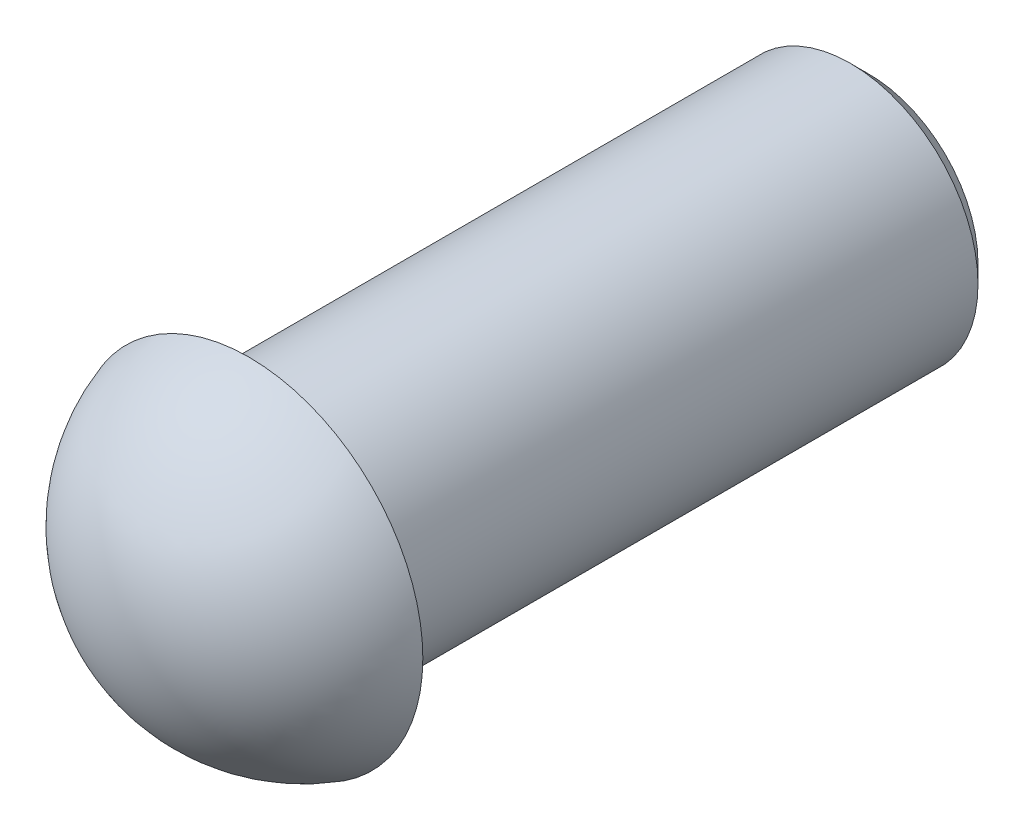
SolidWorks part; units mm, degrees
ref_plane "Plan d'appui" through (0, 0, 0) normal (0, 0, 1) x (1, 0, 0)
ref_plane "Dessus" through (0, 0, 0) normal (0, 1, 0) x (1, 0, 0)
ref_plane "Droite" through (0, 0, 0) normal (1, 0, 0) x (0, 0, -1)
ref_axis "Axe1" through (0, 0, -50) along (0, 0, 1)
sketch "Esquisse1" plane through (0, 0, 0) normal (0, 0, 1) x (1, 0, 0)
  circle A0 centre (0, 0) radius 3.5
  circle A1 centre (0, 0) radius 3.5 construction
extrude "Base-Extrusion" add sketch "Esquisse1" against normal blind 17
sketch "Esquisse3" plane through (0, 0, 0) normal (1, 0, 0) x (0, 0, -1)
  line L0 (0, 0) -> (8.9511, 0) construction
  line L1 (17, 0) -> (0, 0) construction
  line L2 (0, 0) -> (0, 4.7697)
  line L3 (0, 0) -> (-3.5, 0)
  arc A0 (0, 4.7697) -> (-3.5, 0) centre (1.5, 0) ccw
  dimension "D1" = 5
  dimension "D2" = 1.5
revolve "Boss.-Révol.1" add sketch "Esquisse3" angle 360 about L0
chamfer "Chanfrein1" distance 0.5 angle 45 1 edges at (3.5, 0, -17)
